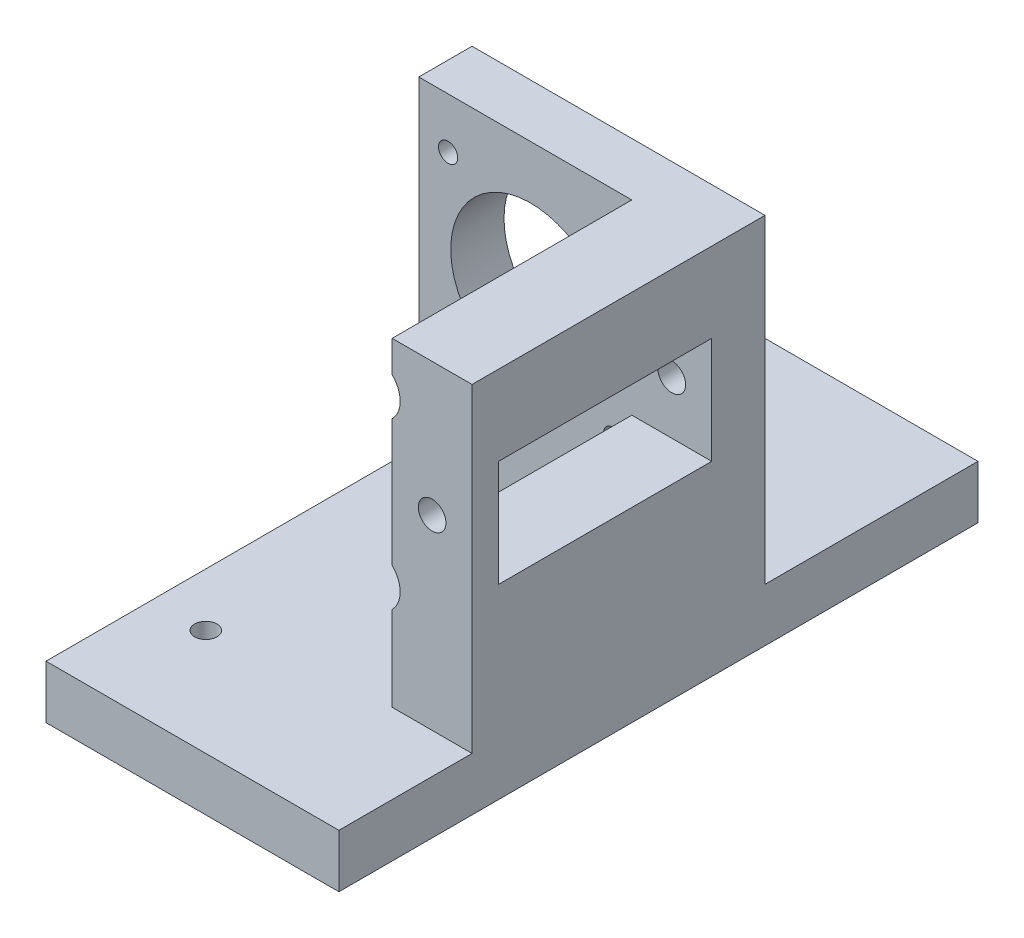
SolidWorks part; units mm, degrees
ref_plane "Front Plane" through (0, 0, 0) normal (0, 0, 1) x (1, 0, 0)
ref_plane "Top Plane" through (0, 0, 0) normal (0, 1, 0) x (1, 0, 0)
ref_plane "Right Plane" through (0, 0, 0) normal (1, 0, 0) x (0, 0, -1)
sketch "Sketch4" plane through (0, 0, 0) normal (0, 1, 0) x (1, 0, 0)
  line L1 (0, 0) -> (40, 0)
  line L2 (0, 0) -> (0, 80)
  line L3 (0, 80) -> (40, 80)
  line L4 (40, 0) -> (40, 80)
  dimension "D1" = 80
  dimension "D2" = 40
extrude "Boss-Extrude4" add sketch "Sketch4" along normal blind 5
sketch "Sketch5" plane through (0, 5, 0) normal (0, 1, 0) x (1, 0, 0)
  line L0 (40, 40) -> (30, 40)
  line L1 (30, 30) -> (30, 50) construction
  line L2 (40, 50) -> (30, 50)
  line L3 (30, 50) -> (30, 55)
  line L4 (0, 80) -> (0, 0)
  line L5 (0, 0) -> (40, 0)
  line L6 (40, 0) -> (40, 80)
  line L7 (40, 80) -> (0, 80)
  line L8 (0, 80) -> (0, 0)
  line L9 (0, 0) -> (40, 0)
  line L10 (40, 0) -> (40, 80)
  line L11 (40, 80) -> (0, 80)
  line L12 (30, 55) -> (40, 55)
  line L13 (40, 55) -> (40, 50)
  line L14 (40, 30) -> (30, 30)
  line L15 (30, 30) -> (30, 25)
  line L16 (30, 25) -> (40, 25)
  line L17 (40, 25) -> (40, 30)
  point P9 (30, 40)
  line M11 (40, 0) -> (40, 80)
  dimension "D2" = 10
  dimension "D3" = 10
  dimension "D4" = 5
  dimension "D5" = 5
  dimension "D1" = 0
extrude "Boss-Extrude6" add sketch "Sketch5" along normal blind 50 contours L12 L3 L2 M11 | L15 L16 L10 L14 region at (35, 5, -52.5) region at (35, 5, -27.5)
sketch "Sketch7" plane through (0, 0, -50) normal (0, 0, 1) x (1, 0, 0)
  line L1 (30, 5) -> (40, 5)
  line L2 (30, 5) -> (30, 30)
  line L3 (30, 30) -> (40, 30)
  line L4 (40, 5) -> (40, 30)
  line L5 (40, 55) -> (40, 5) construction
  line L7 (30, 55) -> (40, 55)
  line L8 (30, 55) -> (30, 50)
  line L9 (30, 50) -> (40, 50)
  line L10 (40, 55) -> (40, 50)
  dimension "D1" = 25
  dimension "D2" = 10
  dimension "D3" = 5
extrude "Boss-Extrude7" add sketch "Sketch7" along normal up to surface (20 mm away) contours L8 L7 L10 L9 | L2 L1 L4 L3 up to face at (35, 30, -30)
sketch "Sketch8" plane through (0, 0, -80) normal (0, 0, -1) x (-1, 0, 0)
  line L4 (-40, 0) -> (0, 0)
  line L5 (0, 0) -> (0, 5)
  line L6 (0, 5) -> (-40, 5)
  line L7 (-40, 5) -> (-40, 0)
  line L8 (-40, 0) -> (0, 0)
  line L9 (0, 0) -> (0, 5)
  line L10 (0, 5) -> (-40, 5)
  line L11 (-40, 5) -> (-40, 0)
  dimension "D1" = 0
extrude "Boss-Extrude8" add sketch "Sketch8" along normal blind 20 contours L8 L9 L10 L11
sketch "Sketch9" plane through (0, 0, 0) normal (-1, 0, 0) x (0, 0, 1)
  line L4 (-100, 0) -> (0, 0)
  line L5 (0, 0) -> (0, 5)
  line L6 (0, 5) -> (-100, 5)
  line L7 (-100, 5) -> (-100, 0)
  line L8 (-100, 0) -> (0, 0)
  line L9 (0, 0) -> (0, 5)
  line L10 (0, 5) -> (-100, 5)
  line L11 (-100, 5) -> (-100, 0)
  dimension "D1" = 0
extrude "Boss-Extrude9" add sketch "Sketch9" along normal blind 10
sketch "Sketch10" plane through (30, 0, 0) normal (-1, 0, 0) x (0, 0, 1)
  line L0 (-25, 5) -> (-55, 5) construction
  line L1 (-55, 55) -> (-50, 55)
  line L2 (-55, 55) -> (-55, 5)
  line L3 (-55, 5) -> (-50, 5)
  line L4 (-50, 55) -> (-50, 5)
  dimension "D1" = 5
extrude "Boss-Extrude10" add sketch "Sketch10" along normal blind 40 contours L2 L1 L4 L3
sketch "Sketch11" plane through (0, 55, 0) normal (0, 1, 0) x (1, 0, 0)
  line L6 (40, 55) -> (-10, 55)
  line L7 (-10, 55) -> (-10, 50)
  line L8 (-10, 50) -> (30, 50)
  line L9 (30, 50) -> (30, 25)
  line L10 (30, 25) -> (40, 25)
  line L11 (40, 25) -> (40, 55)
  line L12 (40, 55) -> (-10, 55)
  line L13 (-10, 55) -> (-10, 50)
  line L14 (-10, 50) -> (30, 50)
  line L15 (30, 50) -> (30, 25)
  line L16 (30, 25) -> (40, 25)
  line L17 (40, 25) -> (40, 55)
  dimension "D1" = 0
extrude "Boss-Extrude11" add sketch "Sketch11" along normal blind 10
sketch "Sketch12" plane through (0, 0, -50) normal (0, 0, 1) x (1, 0, 0)
  line L0 (30, 50) -> (30, 30)
  line L1 (30, 40) -> (26, 40)
  line L2 (0.3934, 50.6066) -> (-3.227, 54.227)
  line L3 (-10, 61) -> (32, 61)
  line L4 (-10, 61) -> (-10, 19)
  line L5 (-10, 19) -> (32, 19)
  line L6 (32, 61) -> (32, 19)
  line L7 (-10, 61) -> (32, 19) construction
  line L8 (30, 30) -> (40, 30)
  line L9 (40, 30) -> (40, 50)
  line L10 (40, 50) -> (30, 50)
  line L11 (30, 50) -> (30, 65)
  line L12 (30, 65) -> (-10, 65)
  line L13 (-10, 65) -> (-10, 5)
  line L14 (-10, 5) -> (30, 5)
  line L15 (30, 5) -> (30, 30)
  line L16 (30, 30) -> (40, 30)
  line L17 (40, 30) -> (40, 50)
  line L18 (40, 50) -> (30, 50)
  line L19 (30, 50) -> (30, 65)
  line L20 (30, 65) -> (-10, 65)
  line L21 (-10, 65) -> (-10, 5)
  line L22 (-10, 5) -> (30, 5)
  line L23 (30, 5) -> (30, 30)
  line L24 (-10, 19) -> (32, 61) construction
  line L25 (-2.6998, 24.5002) -> (-4.4998, 24.5002) construction
  line L26 (24.6998, 24.5002) -> (-2.6998, 24.5002)
  line L27 (26.4998, 26.3002) -> (26.4998, 53.6998)
  line L28 (24.6998, 55.4998) -> (-2.6998, 55.4998)
  line L29 (-4.4998, 26.3002) -> (-4.4998, 53.6998)
  line L30 (26.4998, 24.5002) -> (-4.4998, 55.4998) construction
  line L31 (26.4998, 55.4998) -> (-4.4998, 24.5002) construction
  line L32 (26.4998, 24.5002) -> (24.6998, 24.5002) construction
  line L33 (26.4998, 24.5002) -> (26.4998, 26.3002) construction
  line L34 (26.4998, 53.6998) -> (26.4998, 55.4998) construction
  line L35 (26.4998, 55.4998) -> (24.6998, 55.4998) construction
  line L36 (11, 40) -> (0.3934, 50.6066) construction
  line L37 (26, 40) -> (11, 40) construction
  line L38 (-3.227, 54.227) -> (-4.4998, 55.4998) construction
  line L39 (-4.4998, 53.6998) -> (-4.4998, 55.4998) construction
  line L40 (-2.6998, 55.4998) -> (-4.4998, 55.4998) construction
  line L41 (-4.4998, 24.5002) -> (-4.4998, 26.3002) construction
  circle A0 centre (11, 40) radius 15
  circle A1 centre (-4.4998, 55.4998) radius 1.8
  circle A2 centre (26.4998, 55.4998) radius 1.8
  circle A3 centre (26.4998, 24.5002) radius 1.8
  circle A4 centre (-4.4998, 24.5002) radius 1.8
  dimension "D2" = 19
  dimension "D3" = 30
  dimension "D6" = 3.6
  dimension "D7" = 3.6
  dimension "D1" = 0
  dimension "D4" = 42
  dimension "D5" = 21.92
extrude "Cut-Extrude1" cut sketch "Sketch12" against normal up to surface (5 mm away) contours A0 | A1 | A2 | A4 | A3 region at (11, 40, -50) region at (-4.4998, 55.4998, -50) up to face at (15, 35, -55)
sketch "Sketch13" plane through (0, 0, -50) normal (0, 0, 1) x (1, 0, 0)
  line L0 (40, 40) -> (35, 40) construction
  line L8 (30, 30) -> (40, 30)
  line L9 (40, 30) -> (40, 50)
  line L10 (40, 50) -> (30, 50)
  line L11 (30, 50) -> (30, 65)
  line L12 (30, 65) -> (-10, 65)
  line L13 (-10, 65) -> (-10, 5)
  line L14 (-10, 5) -> (30, 5)
  line L15 (30, 5) -> (30, 30)
  line L16 (30, 30) -> (40, 30)
  line L17 (40, 30) -> (40, 50)
  line L18 (40, 50) -> (30, 50)
  line L19 (30, 50) -> (30, 65)
  line L20 (30, 65) -> (-10, 65)
  line L21 (-10, 65) -> (-10, 5)
  line L22 (-10, 5) -> (30, 5)
  line L23 (30, 5) -> (30, 30)
  circle A0 centre (35, 40) radius 2.25
  dimension "D3" = 4.5
  dimension "D2" = 5
  dimension "D1" = 0
extrude "Cut-Extrude2" cut sketch "Sketch13" against normal through all both and the other way through all contours A0
sketch "Sketch14" plane through (0, 0, -25) normal (0, 0, 1) x (1, 0, 0)
  circle A0 centre (35, 40) radius 2.25 construction
  circle A1 centre (35, 40) radius 2.25
  circle A2 centre (35, 40) radius 4
  dimension "D1" = 8
extrude "Cut-Extrude4" cut sketch "Sketch14" against normal blind 2 contours A1 | A2
sketch "Sketch15" plane through (0, 0, -55) normal (0, 0, -1) x (-1, 0, 0)
  circle A0 centre (-35, 40) radius 2.25 construction
  circle A1 centre (-35, 40) radius 2.25
  circle A2 centre (-35, 40) radius 4
  dimension "D1" = 8
extrude "Cut-Extrude5" cut sketch "Sketch15" against normal blind 2
sketch "Sketch17" plane through (0, 0, -25) normal (0, 0, 1) x (1, 0, 0)
  line L0 (26.4998, 55.4998) -> (26.4998, 24.5002)
  circle A0 centre (26.4998, 55.4998) radius 1.8 construction
  circle A1 centre (26.4998, 55.4998) radius 1.8
  circle A2 centre (26.4998, 55.4998) radius 5
  circle A3 centre (26.4998, 24.5002) radius 5
  line M4 (30, 65) -> (30, 5)
  dimension "D1" = 10
  dimension "D2" = 10
extrude "Cut-Extrude6" cut sketch "Sketch17" against normal up to surface (25 mm away) contours A2 A1 M4 | A3 M4 | A3 M4 | A2 M4 region at (21.9924, 57.3406, -25) region at (26.0733, 24.5002, -25) region at (30.6084, 55.4998, -25) region at (30.6084, 24.5002, -25) up to face at (37.25, 40, -50)
sketch "Sketch19" plane through (0, 0, -55) normal (0, 0, -1) x (-1, 0, 0)
  line L4 (10, 5) -> (10, 65)
  line L5 (10, 65) -> (-40, 65)
  line L6 (-40, 65) -> (-40, 5)
  line L7 (-40, 5) -> (10, 5)
  line L8 (10, 5) -> (10, 65)
  line L9 (10, 65) -> (-40, 65)
  line L10 (-40, 65) -> (-40, 5)
  line L11 (-40, 5) -> (10, 5)
  circle A0 centre (4.4998, 55.4998) radius 1.8 construction
  circle A1 centre (4.4998, 24.5002) radius 1.8 construction
  circle A2 centre (-26.4998, 24.5002) radius 1.8 construction
  circle A3 centre (-11, 40) radius 15 construction
  circle A4 centre (-35, 40) radius 4 construction
  circle A6 centre (-26.4998, 55.4998) radius 1.8 construction
  circle A7 centre (4.4998, 55.4998) radius 1.8
  circle A8 centre (4.4998, 24.5002) radius 1.8
  circle A9 centre (-26.4998, 24.5002) radius 1.8
  circle A10 centre (-11, 40) radius 15
  circle A11 centre (-35, 40) radius 4
  circle A13 centre (-26.4998, 55.4998) radius 1.8
  dimension "D1" = 0
extrude "Boss-Extrude13" add sketch "Sketch19" along normal blind 5
sketch "Sketch20" plane through (0, 0, -53) normal (0, 0, -1) x (-1, 0, 0)
  circle A0 centre (-35, 40) radius 2.25 construction
  circle A1 centre (-35, 40) radius 4
  circle A2 centre (-35, 40) radius 4
  circle A3 centre (-35, 40) radius 2.25
  dimension "D1" = 0
extrude "Boss-Extrude14" add sketch "Sketch20" along normal blind 5
sketch "Sketch21" plane through (40, 0, 0) normal (1, 0, 0) x (0, 0, -1)
  line L0 (50, 50) -> (50, 30) construction
  line L1 (30, 50) -> (30, 30) construction
  line L2 (30, 50) -> (50, 50) construction
  line L3 (30, 30) -> (50, 30) construction
  line L4 (50, 50) -> (50, 30)
  line L5 (30, 50) -> (30, 30)
  line L6 (30, 50) -> (50, 50)
  line L7 (30, 30) -> (50, 30)
  line L8 (100, 5) -> (60, 5)
  line L9 (60, 5) -> (60, 65)
  line L10 (60, 65) -> (25, 65)
  line L11 (25, 65) -> (25, 5)
  line L12 (25, 5) -> (0, 5)
  line L13 (0, 5) -> (0, 0)
  line L14 (0, 0) -> (100, 0)
  line L15 (100, 0) -> (100, 5)
  line L16 (100, 5) -> (60, 5)
  line L17 (60, 5) -> (60, 65)
  line L18 (60, 65) -> (25, 65)
  line L19 (25, 65) -> (25, 5)
  line L20 (25, 5) -> (0, 5)
  line L21 (0, 5) -> (0, 0)
  line L22 (0, 0) -> (100, 0)
  line L23 (100, 0) -> (100, 5)
  dimension "D1" = 0
extrude "Boss-Extrude15" add sketch "Sketch21" along normal blind 5
sketch "Sketch22" plane through (0, 0, -60) normal (0, 0, -1) x (-1, 0, 0)
  circle A0 centre (-35, 40) radius 4 construction
  circle A1 centre (-35, 40) radius 4
extrude "Boss-Extrude16" add sketch "Sketch22" against normal up to surface (10 mm away) up to face at (26.0833, 38.3333, -50)
sketch "Sketch23" plane through (0, 0, -25) normal (0, 0, 1) x (1, 0, 0)
  circle A0 centre (35, 40) radius 4 construction
  circle A1 centre (35, 40) radius 4
extrude "Boss-Extrude17" add sketch "Sketch23" against normal up to surface (5 mm away) up to face at (37.25, 40, -30)
sketch "Sketch24" plane through (0, 0, -30) normal (0, 0, -1) x (-1, 0, 0)
  line L0 (-30, 30) -> (-45, 50) construction
  line L1 (-30, 50) -> (-45, 30) construction
  line L4 (-30, 50) -> (-45, 50)
  line L5 (-45, 50) -> (-45, 30)
  line L6 (-45, 30) -> (-30, 30)
  line L7 (-30, 30) -> (-30, 50)
  line L8 (-30, 50) -> (-45, 50)
  line L9 (-45, 50) -> (-45, 30)
  line L10 (-45, 30) -> (-30, 30)
  line L11 (-30, 30) -> (-30, 50)
  circle A0 centre (-37.5, 40) radius 2.6
  dimension "D2" = 5.2
  dimension "D1" = 0
extrude "Cut-Extrude7" cut sketch "Sketch24" against normal through all both and the other way through all contours A0
sketch "Sketch25" plane through (0, 0, 0) normal (0, -1, 0) x (1, 0, 0)
  line L4 (45, 0) -> (-10, 0)
  line L5 (-10, 0) -> (-10, -100)
  line L6 (-10, -100) -> (45, -100)
  line L7 (45, -100) -> (45, 0)
  line L8 (45, 0) -> (-10, 0)
  line L9 (-10, 0) -> (-10, -100)
  line L10 (-10, -100) -> (45, -100)
  line L11 (45, -100) -> (45, 0)
  dimension "D1" = 0
extrude "Boss-Extrude18" add sketch "Sketch25" along normal blind 5
sketch "Sketch26" plane through (0, 0, 0) normal (0, 0, 1) x (1, 0, 0)
  line L4 (-10, 5) -> (-10, -5)
  line L5 (-10, -5) -> (45, -5)
  line L6 (45, -5) -> (45, 5)
  line L7 (45, 5) -> (-10, 5)
  line L8 (-10, 5) -> (-10, -5)
  line L9 (-10, -5) -> (45, -5)
  line L10 (45, -5) -> (45, 5)
  line L11 (45, 5) -> (-10, 5)
  dimension "D1" = 0
extrude "Boss-Extrude19" add sketch "Sketch26" along normal blind 20
sketch "Sketch27" plane through (30, 0, 0) normal (-1, 0, 0) x (0, 0, 1)
  line L1 (-30, 50) -> (-25, 50)
  line L2 (-30, 50) -> (-30, 30)
  line L3 (-30, 30) -> (-25, 30)
  line L4 (-25, 50) -> (-25, 30)
  line L5 (-25, 51.9293) -> (-25, 28.0707) construction
  dimension "D1" = 5
  dimension "D2" = 20
extrude "Cut-Extrude8" cut sketch "Sketch27" against normal blind 15
sketch "Sketch28" plane through (0, 0, -25) normal (0, 0, 1) x (1, 0, 0)
  line L5 (45, 5) -> (45, 30)
  line L6 (45, 30) -> (30, 30)
  line L7 (30, 30) -> (30, 28.0707)
  line L8 (30, 20.9297) -> (30, 5)
  line L9 (30, 5) -> (45, 5)
  line L10 (45, 5) -> (45, 30)
  line L11 (45, 30) -> (30, 30)
  line L12 (30, 30) -> (30, 28.0707)
  line L13 (30, 20.9297) -> (30, 5)
  line L14 (30, 5) -> (45, 5)
  line L15 (30, 51.9293) -> (30, 50)
  line L16 (30, 50) -> (45, 50)
  line L17 (45, 50) -> (45, 65)
  line L18 (45, 65) -> (30, 65)
  line L19 (30, 65) -> (30, 59.0703)
  line L20 (30, 51.9293) -> (30, 50)
  line L21 (30, 50) -> (45, 50)
  line L22 (45, 50) -> (45, 65)
  line L23 (45, 65) -> (30, 65)
  line L24 (30, 65) -> (30, 59.0703)
  arc A1 (30, 20.9297) -> (30, 28.0707) centre (26.4998, 24.5002) ccw
  arc A2 (30, 20.9297) -> (30, 28.0707) centre (26.4998, 24.5002) ccw
  arc A3 (30, 51.9293) -> (30, 59.0703) centre (26.4998, 55.4998) ccw
  arc A4 (30, 51.9293) -> (30, 59.0703) centre (26.4998, 55.4998) ccw
  dimension "D1" = 0
  dimension "D2" = 0
extrude "Boss-Extrude20" add sketch "Sketch28" along normal blind 20
sketch "Sketch29" plane through (0, 30, 0) normal (0, 1, 0) x (1, 0, 0)
  line L7 (30, 5) -> (45, 5)
  line L8 (30, 5) -> (30, 10)
  line L9 (30, 10) -> (45, 10)
  line L10 (45, 5) -> (45, 10)
  line L11 (45, 5) -> (45, 50) construction
  dimension "D1" = 5
  dimension "D2" = 15
extrude "Boss-Extrude21" add sketch "Sketch29" along normal blind 20
sketch "Sketch30" plane through (0, 0, -60) normal (0, 0, -1) x (-1, 0, 0)
  circle A0 centre (-37.5, 40) radius 2.6 construction
  circle A1 centre (-37.5, 40) radius 2.6
extrude "Cut-Extrude9" cut sketch "Sketch30" against normal blind 60
sketch "Sketch31" plane through (0, -5, 0) normal (0, -1, 0) x (1, 0, 0)
  line L0 (-10, 20) -> (0, 20) construction
  line L1 (-10, 20) -> (45, 20) construction
  line L2 (0, 20) -> (0, 0) construction
  line L3 (0, 0) -> (0, -80) construction
  circle A0 centre (0, 0) radius 2.1
  circle A1 centre (0, -80) radius 2.1
  dimension "D3" = 4.2
  dimension "D4" = 4.2
  dimension "D1" = 20
  dimension "D2" = 80
extrude "Cut-Extrude10" cut sketch "Sketch31" against normal blind 10 contours A1 | A0
